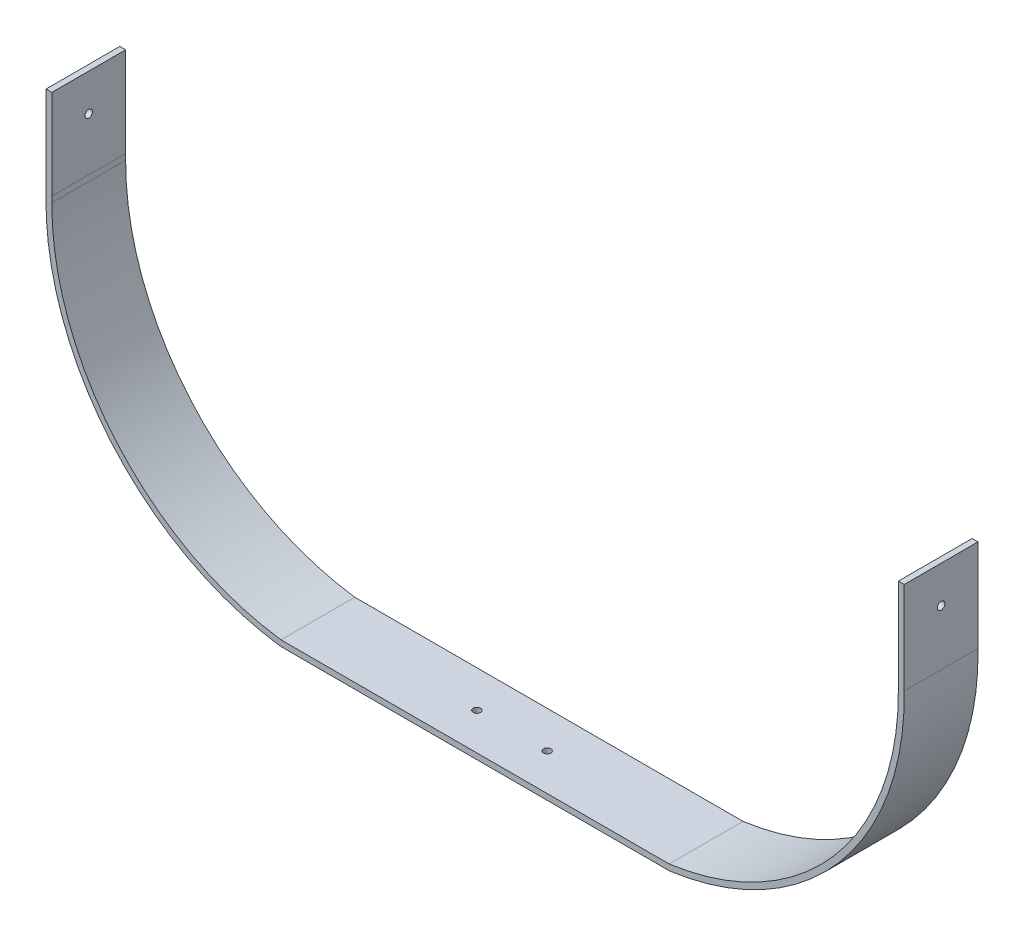
SolidWorks part; units mm, degrees
ref_plane "Front Plane" through (0, 0, 0) normal (0, 0, 1) x (1, 0, 0)
ref_plane "Top Plane" through (0, 0, 0) normal (0, 1, 0) x (1, 0, 0)
ref_plane "Right Plane" through (0, 0, 0) normal (1, 0, 0) x (0, 0, -1)
sketch "Sketch1" plane through (0, 0, 0) normal (0, 0, 1) x (1, 0, 0)
  line L0 (-80, 0) -> (80, 0)
  line L2 (232.5, 148) -> (232.5, 198)
  line L4 (-232.5, 148) -> (-232.5, 198)
  line L5 (-232.5, 148) -> (232.5, 148) construction
  line L6 (-232.5, 198) -> (232.5, 198) construction
  line L7 (229.325, 149.3431) -> (229.325, 198)
  line L11 (-229.325, 149.3431) -> (-229.325, 198)
  line L12 (-232.5, 198) -> (-229.325, 198)
  line L13 (229.325, 198) -> (232.5, 198)
  line L14 (80, 0) -> (232.5, 148) construction
  line L15 (78.7126, 3.175) -> (229.325, 149.3431) construction
  line L16 (-80, 0) -> (-232.5, 148) construction
  line L17 (-78.7126, 3.175) -> (-229.325, 149.3431) construction
  line L18 (-80, 0) -> (-105.4, 0)
  line L19 (-80, 3.18) -> (80, 3.18)
  line L20 (-80, 3.18) -> (-105.1852, 3.18)
  line L21 (-229.325, 149.3431) -> (-229.3406, 146.1631)
  line L22 (-229.3406, 146.1631) -> (229.325, 146.1631) construction
  line L25 (80, 0) -> (105.4, 0)
  line L26 (80, 3.18) -> (105.1852, 3.18)
  line L31 (229.325, 149.3431) -> (229.325, 146.1631)
  line L33 (-229.3406, 146.1631) -> (-229.3406, 146.1631) construction
  line L34 (-229.3406, 146.1631) -> (-229.3406, 146.1631) construction
  line L35 (-229.3406, 146.1631) -> (-229.3406, 146.1631) construction
  line L36 (-78.7126, 3.175) -> (78.7126, 3.175) construction
  arc A0 (-105.4, 0) -> (-232.5, 148) centre (-85.7667, 145.4364) cw
  arc A1 (-105.1852, 3.18) -> (-229.3406, 146.1631) centre (-85.7667, 145.4364) cw
  arc A5 (229.325, 146.1631) -> (105.1852, 3.18) centre (85.7512, 145.4343) cw
  arc A6 (105.4, 0) -> (232.5, 148) centre (85.7667, 145.4364) ccw
  point P8 (0, 0)
  point P26 (0, 0)
  dimension "D1" = 160
  dimension "D2" = 465
  dimension "D3" = 198
  dimension "D4" = 50
  dimension "D6" = 25.4
  dimension "D5" = 3.175
  dimension "D7" = 3.18
extrude "Boss-Extrude1" add sketch "Sketch1" along normal blind 40
sketch "Sketch3" plane through (0, 0, 0) normal (0, 1, 0) x (1, 0, 0)
  line L0 (-105.4, -20) -> (-19.05, -20) construction
  line L2 (-19.05, -20) -> (19.05, -20) construction
  line L3 (19.05, -20) -> (105.4, -20) construction
  line L5 (105.4, -40) -> (105.4, 0) construction
  circle A0 centre (-19.05, -20) radius 2
  circle A1 centre (19.05, -20) radius 2
  point P2 (105.4, -20)
  dimension "D2" = 4
  dimension "D1" = 38.1
extrude "Cut-Extrude1" cut sketch "Sketch3" along normal through all
sketch "Sketch4" plane through (-232.5, 0, 0) normal (-1, 0, 0) x (0, 0, 1)
  line L0 (20, 198) -> (20, 148) construction
  line L1 (40, 198) -> (0, 198) construction
  line L3 (0, 178) -> (40, 178) construction
  line L4 (0, 148) -> (0, 198) construction
  line L5 (40, 148) -> (40, 198) construction
  line L6 (40, 148) -> (0, 148) construction
  circle A0 centre (20, 178) radius 2.0479
  point P4 (20, 148)
  dimension "D2" = 4.0958
  dimension "D1" = 20
extrude "Cut-Extrude2" cut sketch "Sketch4" against normal through all both
